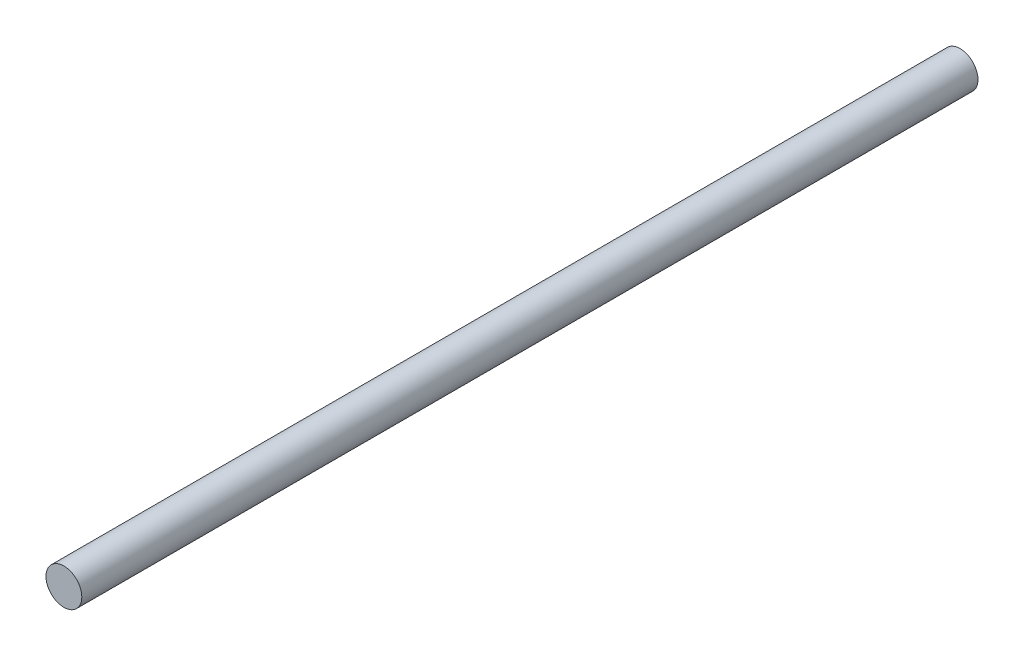
SolidWorks part; units mm, degrees
ref_plane "Front Plane" through (0, 0, 0) normal (0, 0, 1) x (1, 0, 0)
ref_plane "Top Plane" through (0, 0, 0) normal (0, 1, 0) x (1, 0, 0)
ref_plane "Right Plane" through (0, 0, 0) normal (1, 0, 0) x (0, 0, -1)
sketch "Sketch1" plane through (0, 0, 0) normal (0, 0, 1) x (1, 0, 0)
  circle A0 centre (0, 0) radius 3
  dimension "D1" = 6
extrude "Boss-Extrude1" add sketch "Sketch1" along normal blind 100 and the other way blind 50
